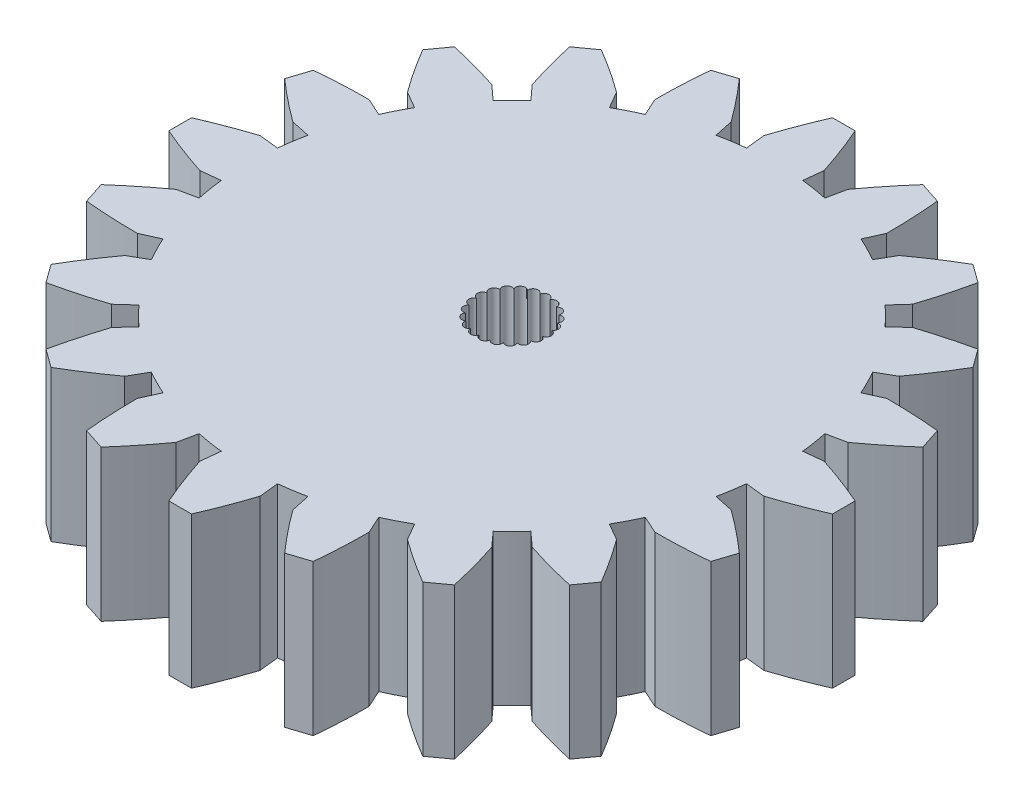
SolidWorks part; units mm, degrees
ref_plane "Front Plane" through (0, 0, 0) normal (0, 0, 1) x (1, 0, 0)
ref_plane "Top Plane" through (0, 0, 0) normal (0, 1, 0) x (1, 0, 0)
ref_plane "Right Plane" through (0, 0, 0) normal (1, 0, 0) x (0, 0, -1)
sketch "Sketch2" plane through (0, 0, 0) normal (0, 1, 0) x (1, 0, 0)
  line L0 (0, -10.2886) -> (0, 10.2886) construction
  line L1 (0, 0) -> (0.6267, 4.1579) construction
  line L2 (0, 0) -> (-0.6267, 4.1579) construction
  line L3 (0, 0) -> (1.373, 17.4461) construction
  line L4 (0, 0) -> (-1.373, 17.4461) construction
  line L5 (2, 18.6871) -> (1.8623, 17.4006)
  line L6 (-2, 18.6871) -> (-1.8623, 17.4006)
  line L7 (-0.75, 21.9872) -> (0.75, 21.9872)
  line L8 (6.0811, 21.1428) -> (7.5077, 20.6793)
  line L9 (7.6768, 17.1545) -> (7.1483, 15.9735)
  line L10 (3.8725, 18.3906) -> (3.6059, 17.1245)
  line L11 (12.317, 18.2289) -> (13.5305, 17.3472)
  line L12 (12.6021, 13.9426) -> (11.7345, 12.9828)
  line L13 (9.366, 16.2938) -> (8.7212, 15.172)
  line L14 (17.3472, 13.5305) -> (18.2289, 12.317)
  line L15 (16.2938, 9.366) -> (15.172, 8.7212)
  line L16 (13.9426, 12.6021) -> (12.9828, 11.7345)
  line L17 (20.6793, 7.5077) -> (21.1428, 6.0811)
  line L18 (18.3906, 3.8725) -> (17.1245, 3.6059)
  line L19 (17.1545, 7.6768) -> (15.9735, 7.1483)
  line L20 (21.9872, 0.75) -> (21.9872, -0.75)
  line L21 (18.6871, -2) -> (17.4006, -1.8623)
  line L22 (18.6871, 2) -> (17.4006, 1.8623)
  line L23 (21.1428, -6.0811) -> (20.6793, -7.5077)
  line L24 (17.1545, -7.6768) -> (15.9735, -7.1483)
  line L25 (18.3906, -3.8725) -> (17.1245, -3.6059)
  line L26 (18.2289, -12.317) -> (17.3472, -13.5305)
  line L27 (13.9426, -12.6021) -> (12.9828, -11.7345)
  line L28 (16.2938, -9.366) -> (15.172, -8.7212)
  line L29 (13.5305, -17.3472) -> (12.317, -18.2289)
  line L30 (9.366, -16.2938) -> (8.7212, -15.172)
  line L31 (12.6021, -13.9426) -> (11.7345, -12.9828)
  line L32 (7.5077, -20.6793) -> (6.0811, -21.1428)
  line L33 (3.8725, -18.3906) -> (3.6059, -17.1245)
  line L34 (7.6768, -17.1545) -> (7.1483, -15.9735)
  line L35 (0.75, -21.9872) -> (-0.75, -21.9872)
  line L36 (-2, -18.6871) -> (-1.8623, -17.4006)
  line L37 (2, -18.6871) -> (1.8623, -17.4006)
  line L38 (-6.0811, -21.1428) -> (-7.5077, -20.6793)
  line L39 (-7.6768, -17.1545) -> (-7.1483, -15.9735)
  line L40 (-3.8725, -18.3906) -> (-3.6059, -17.1245)
  line L41 (-12.317, -18.2289) -> (-13.5305, -17.3472)
  line L42 (-12.6021, -13.9426) -> (-11.7345, -12.9828)
  line L43 (-9.366, -16.2938) -> (-8.7212, -15.172)
  line L44 (-17.3472, -13.5305) -> (-18.2289, -12.317)
  line L45 (-16.2938, -9.366) -> (-15.172, -8.7212)
  line L46 (-13.9426, -12.6021) -> (-12.9828, -11.7345)
  line L47 (-20.6793, -7.5077) -> (-21.1428, -6.0811)
  line L48 (-18.3906, -3.8725) -> (-17.1245, -3.6059)
  line L49 (-17.1545, -7.6768) -> (-15.9735, -7.1483)
  line L50 (-21.9872, -0.75) -> (-21.9872, 0.75)
  line L51 (-18.6871, 2) -> (-17.4006, 1.8623)
  line L52 (-18.6871, -2) -> (-17.4006, -1.8623)
  line L53 (-21.1428, 6.0811) -> (-20.6793, 7.5077)
  line L54 (-17.1545, 7.6768) -> (-15.9735, 7.1483)
  line L55 (-18.3906, 3.8725) -> (-17.1245, 3.6059)
  line L56 (-18.2289, 12.317) -> (-17.3472, 13.5305)
  line L57 (-13.9426, 12.6021) -> (-12.9828, 11.7345)
  line L58 (-16.2938, 9.366) -> (-15.172, 8.7212)
  line L59 (-13.5305, 17.3472) -> (-12.317, 18.2289)
  line L60 (-9.366, 16.2938) -> (-8.7212, 15.172)
  line L61 (-12.6021, 13.9426) -> (-11.7345, 12.9828)
  line L62 (-7.5077, 20.6793) -> (-6.0811, 21.1428)
  line L63 (-3.8725, 18.3906) -> (-3.6059, 17.1245)
  line L64 (-7.6768, 17.1545) -> (-7.1483, 15.9735)
  circle A0 centre (0, 0) radius 18.7939 construction
  circle A1 centre (0, 0) radius 2.2
  circle A2 centre (0, 0) radius 2.45 construction
  arc A3 (-0.3279, 2.1754) -> (0.3279, 2.1754) centre (0, 2.1169) cw
  arc A4 (0.3279, 2.1754) -> (0.9545, 1.9821) centre (0.624, 2.0229) cw
  arc A5 (0.9545, 1.9821) -> (1.4964, 1.6127) centre (1.1925, 1.7491) cw
  arc A6 (1.4964, 1.6127) -> (1.9053, 1.1) centre (1.6551, 1.3199) cw
  arc A7 (1.9053, 1.1) -> (2.1448, 0.4895) centre (1.9706, 0.7734) cw
  arc A8 (2.1448, 0.4895) -> (2.1938, -0.1644) centre (2.111, 0.1582) cw
  arc A9 (2.1938, -0.1644) -> (2.0479, -0.8038) centre (2.0639, -0.4711) cw
  arc A10 (2.0479, -0.8038) -> (1.72, -1.3717) centre (1.8333, -1.0585) cw
  arc A11 (1.72, -1.3717) -> (1.2393, -1.8177) centre (1.4399, -1.5518) cw
  arc A12 (1.2393, -1.8177) -> (0.6485, -2.1023) centre (0.9185, -1.9073) cw
  arc A13 (0.6485, -2.1023) -> (0, -2.2) centre (0.3155, -2.0933) cw
  arc A14 (0, -2.2) -> (-0.6485, -2.1023) centre (-0.3155, -2.0933) cw
  arc A15 (-0.6485, -2.1023) -> (-1.2393, -1.8177) centre (-0.9185, -1.9073) cw
  arc A16 (-1.2393, -1.8177) -> (-1.72, -1.3717) centre (-1.4399, -1.5518) cw
  arc A17 (-1.72, -1.3717) -> (-2.0479, -0.8038) centre (-1.8333, -1.0585) cw
  arc A18 (-2.0479, -0.8038) -> (-2.1938, -0.1644) centre (-2.0639, -0.4711) cw
  arc A19 (-2.1938, -0.1644) -> (-2.1448, 0.4895) centre (-2.111, 0.1582) cw
  arc A20 (-2.1448, 0.4895) -> (-1.9053, 1.1) centre (-1.9706, 0.7734) cw
  arc A21 (-1.9053, 1.1) -> (-1.4964, 1.6127) centre (-1.6551, 1.3199) cw
  arc A22 (-1.4964, 1.6127) -> (-0.9545, 1.9821) centre (-1.1925, 1.7491) cw
  arc A23 (-0.9545, 1.9821) -> (-0.3279, 2.1754) centre (-0.624, 2.0229) cw
  circle A24 centre (0, 0) radius 17.5
  circle A25 centre (0, 0) radius 20 construction
  circle A26 centre (0, 0) radius 22 construction
  arc A27 (0.75, 21.9872) -> (2, 18.6871) centre (-32.4469, 7.5262) cw
  arc A28 (-0.75, 21.9872) -> (-2, 18.6871) centre (32.4469, 7.5262) ccw
  arc A29 (6.0811, 21.1428) -> (3.8725, 18.3906) centre (33.1845, -2.8688) ccw
  arc A30 (7.5077, 20.6793) -> (7.6768, 17.1545) centre (-28.5331, 17.1844) cw
  arc A31 (12.317, 18.2289) -> (9.366, 16.2938) centre (30.6738, -12.983) ccw
  arc A32 (13.5305, 17.3472) -> (12.6021, 13.9426) centre (-21.8263, 25.1606) cw
  arc A33 (17.3472, 13.5305) -> (13.9426, 12.6021) centre (25.1606, -21.8263) ccw
  arc A34 (18.2289, 12.317) -> (16.2938, 9.366) centre (-12.983, 30.6738) cw
  arc A35 (20.6793, 7.5077) -> (17.1545, 7.6768) centre (17.1844, -28.5331) ccw
  arc A36 (21.1428, 6.0811) -> (18.3906, 3.8725) centre (-2.8688, 33.1845) cw
  arc A37 (21.9872, 0.75) -> (18.6871, 2) centre (7.5262, -32.4469) ccw
  arc A38 (21.9872, -0.75) -> (18.6871, -2) centre (7.5262, 32.4469) cw
  arc A39 (21.1428, -6.0811) -> (18.3906, -3.8725) centre (-2.8688, -33.1845) ccw
  arc A40 (20.6793, -7.5077) -> (17.1545, -7.6768) centre (17.1844, 28.5331) cw
  arc A41 (18.2289, -12.317) -> (16.2938, -9.366) centre (-12.983, -30.6738) ccw
  arc A42 (17.3472, -13.5305) -> (13.9426, -12.6021) centre (25.1606, 21.8263) cw
  arc A43 (13.5305, -17.3472) -> (12.6021, -13.9426) centre (-21.8263, -25.1606) ccw
  arc A44 (12.317, -18.2289) -> (9.366, -16.2938) centre (30.6738, 12.983) cw
  arc A45 (7.5077, -20.6793) -> (7.6768, -17.1545) centre (-28.5331, -17.1844) ccw
  arc A46 (6.0811, -21.1428) -> (3.8725, -18.3906) centre (33.1845, 2.8688) cw
  arc A47 (0.75, -21.9872) -> (2, -18.6871) centre (-32.4469, -7.5262) ccw
  arc A48 (-0.75, -21.9872) -> (-2, -18.6871) centre (32.4469, -7.5262) cw
  arc A49 (-6.0811, -21.1428) -> (-3.8725, -18.3906) centre (-33.1845, 2.8688) ccw
  arc A50 (-7.5077, -20.6793) -> (-7.6768, -17.1545) centre (28.5331, -17.1844) cw
  arc A51 (-12.317, -18.2289) -> (-9.366, -16.2938) centre (-30.6738, 12.983) ccw
  arc A52 (-13.5305, -17.3472) -> (-12.6021, -13.9426) centre (21.8263, -25.1606) cw
  arc A53 (-17.3472, -13.5305) -> (-13.9426, -12.6021) centre (-25.1606, 21.8263) ccw
  arc A54 (-18.2289, -12.317) -> (-16.2938, -9.366) centre (12.983, -30.6738) cw
  arc A55 (-20.6793, -7.5077) -> (-17.1545, -7.6768) centre (-17.1844, 28.5331) ccw
  arc A56 (-21.1428, -6.0811) -> (-18.3906, -3.8725) centre (2.8688, -33.1845) cw
  arc A57 (-21.9872, -0.75) -> (-18.6871, -2) centre (-7.5262, 32.4469) ccw
  arc A58 (-21.9872, 0.75) -> (-18.6871, 2) centre (-7.5262, -32.4469) cw
  arc A59 (-21.1428, 6.0811) -> (-18.3906, 3.8725) centre (2.8688, 33.1845) ccw
  arc A60 (-20.6793, 7.5077) -> (-17.1545, 7.6768) centre (-17.1844, -28.5331) cw
  arc A61 (-18.2289, 12.317) -> (-16.2938, 9.366) centre (12.983, 30.6738) ccw
  arc A62 (-17.3472, 13.5305) -> (-13.9426, 12.6021) centre (-25.1606, -21.8263) cw
  arc A63 (-13.5305, 17.3472) -> (-12.6021, 13.9426) centre (21.8263, 25.1606) ccw
  arc A64 (-12.317, 18.2289) -> (-9.366, 16.2938) centre (-30.6738, -12.983) cw
  arc A65 (-7.5077, 20.6793) -> (-7.6768, 17.1545) centre (28.5331, 17.1844) ccw
  arc A66 (-6.0811, 21.1428) -> (-3.8725, 18.3906) centre (-33.1845, -2.8688) cw
  point P7 (0, 0)
  point P30 (1.5692, 19.9383)
  point P78 (0, 0)
  point P226 (0, 0)
  dimension "D1" = 4.4
  dimension "D3" = 4.9
  dimension "D5" = 37.5877
  dimension "D6" = 35
  dimension "D7" = 40
  dimension "D8" = 44
  dimension "D2" = 8.571
  dimension "D9" = 4.5
  dimension "D11" = 1.5
  dimension "D12" = 4
  dimension "D4" = 21
  dimension "D10" = 20
extrude "Boss-Extrude1" add sketch "Sketch2" along normal blind 10 contours A24 A22 A23 A3 A4 A5 A6 A7 A8 A9 A10 | L7 A28 L6 A24 L5 A27 | A30 L8 A29 L10 A24 L9 | A32 L11 A31 L13 A24 L12 | A34 L14 A33 L16 A24 L15 | A36 L17 A35 L19 A24 L18 | A38 L20 A37 L22 A24 L21 | A40 L23 A39 L25 A24 L24 | A42 L26 A41 L28 A24 L27 | A44 L29 A43 L31 A24 L30 | A46 L32 A45 L34 A24 L33 | A48 L35 A47 L37 A24 L36 | A50 L38 A49 L40 A24 L39 | A52 L41 A51 L43 A24 L42 | A54 L44 A53 L46 A24 L45 | A56 L47 A55 L49 A24 L48 | A58 L50 A57 L52 A24 L51 | A60 L53 A59 L55 A24 L54 | A62 L56 A61 L58 A24 L57 | A64 L59 A63 L61 A24 L60 | A66 L62 A65 L64 A24 L63 region at (0, 0, -19.415) region at (2.6602, 0, -16.7957) region at (5.9996, 0, -18.4648) region at (-5.9996, 0, -18.4648) region at (11.4119, 0, -15.7071) region at (-11.4119, 0, -15.7071) region at (15.7071, 0, -11.4119) region at (-15.7071, 0, -11.4119) region at (18.4648, 0, -5.9996) region at (-18.4648, 0, -5.9996) region at (19.415, 0, 0) region at (-19.415, 0, 0) region at (18.4648, 0, 5.9996) region at (-18.4648, 0, 5.9996) region at (15.7071, 0, 11.4119) region at (-15.7071, 0, 11.4119) region at (11.4119, 0, 15.7071) region at (-11.4119, 0, 15.7071) region at (5.9996, 0, 18.4648) region at (-5.9996, 0, 18.4648) region at (0, 0, 19.415)
equation "\"Module\"= 2"
equation "\"Teeth\"= 20"
equation "\"Pitch Diameter\"= \"Module\" * \"Teeth\""
equation "\"Outer Diamter\"= \"Pitch Diameter\" + ( 2 * \"Module\" )"
equation "\"Root Diameter\"= \"Pitch Diameter\" - ( 2.5 * \"Module\" )"
equation "\"Base Diamter\"= \"Pitch Diameter\" * cos ( 20 )"
equation "\"D5@Sketch2\"=\"Base Diamter\""
equation "\"D6@Sketch2\"=\"Root Diameter\""
equation "\"D7@Sketch2\"=\"Pitch Diameter\""
equation "\"D8@Sketch2\"=\"Outer Diamter\""
equation "\"D9@Sketch2\"=90 / \"Teeth\""
